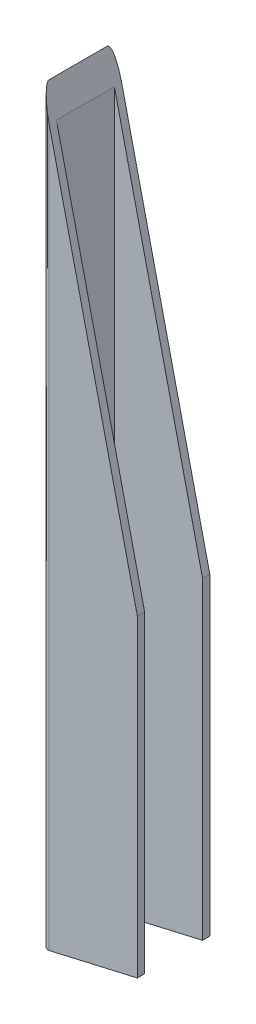
SolidWorks part; units mm, degrees
ref_plane "Спереди" through (0, 0, 0) normal (0, 0, 1) x (1, 0, 0)
ref_plane "Сверху" through (0, 0, 0) normal (0, 1, 0) x (1, 0, 0)
ref_plane "Справа" through (0, 0, 0) normal (1, 0, 0) x (0, 0, -1)
sketch "Эскиз1" plane through (0, 0, 0) normal (0, 1, 0) x (1, 0, 0)
  line L1 (-37, 15) -> (37, 15)
  line L2 (-40, 12) -> (-40, -12)
  line L3 (-37, -15) -> (37, -15)
  line L4 (40, 12) -> (40, -12)
  line L5 (-40, 15) -> (40, -15) construction
  line L6 (-40, -15) -> (40, 15) construction
  arc A0 (-37, 15) -> (-40, 12) centre (-37, 12) ccw
  arc A1 (-40, -12) -> (-37, -15) centre (-37, -12) ccw
  arc A2 (37, -15) -> (40, -12) centre (37, -12) ccw
  arc A3 (37, 15) -> (40, 12) centre (37, 12) cw
  point P0 (0, 0)
  dimension "D1" = 3
extrude "Вытянуть-Тонкостенный1" add sketch "Эскиз1" along normal blind 310 thin thin type one direction reverse wall 3
sketch "Эскиз2" plane through (0, 310, 0) normal (0, 1, 0) x (1, 0, 0)
  line L1 (-0.5, -21.5541) -> (41.1465, -21.5541)
  line L2 (-0.5, -21.5541) -> (-0.5, 20.9728)
  line L3 (-0.5, 20.9728) -> (41.1465, 20.9728)
  line L4 (41.1465, -21.5541) -> (41.1465, 20.9728)
extrude "Вырез-Вытянуть1" cut sketch "Эскиз2" against normal through all
sketch "Эскиз3" plane through (0, 0, 15) normal (0, 0, 1) x (1, 0, 0)
  line L0 (-40, 310) -> (-0.5, 138.9067)
  line L1 (-0.5, 0) -> (-0.5, 310) construction
  line L2 (-0.5, 138.9067) -> (-0.5, 9.1193)
  line L3 (-0.5, 9.1193) -> (-40, 0)
  line L4 (-40, 0) -> (-40, 310)
  line L5 (115.1536, 35.82) -> (-128.4389, -20.4177) construction
  line L6 (-0.5, 310) -> (-0.5, 0) construction
extrude "Вырез-Вытянуть2" cut sketch "Эскиз3" against normal through all flip side to cut
